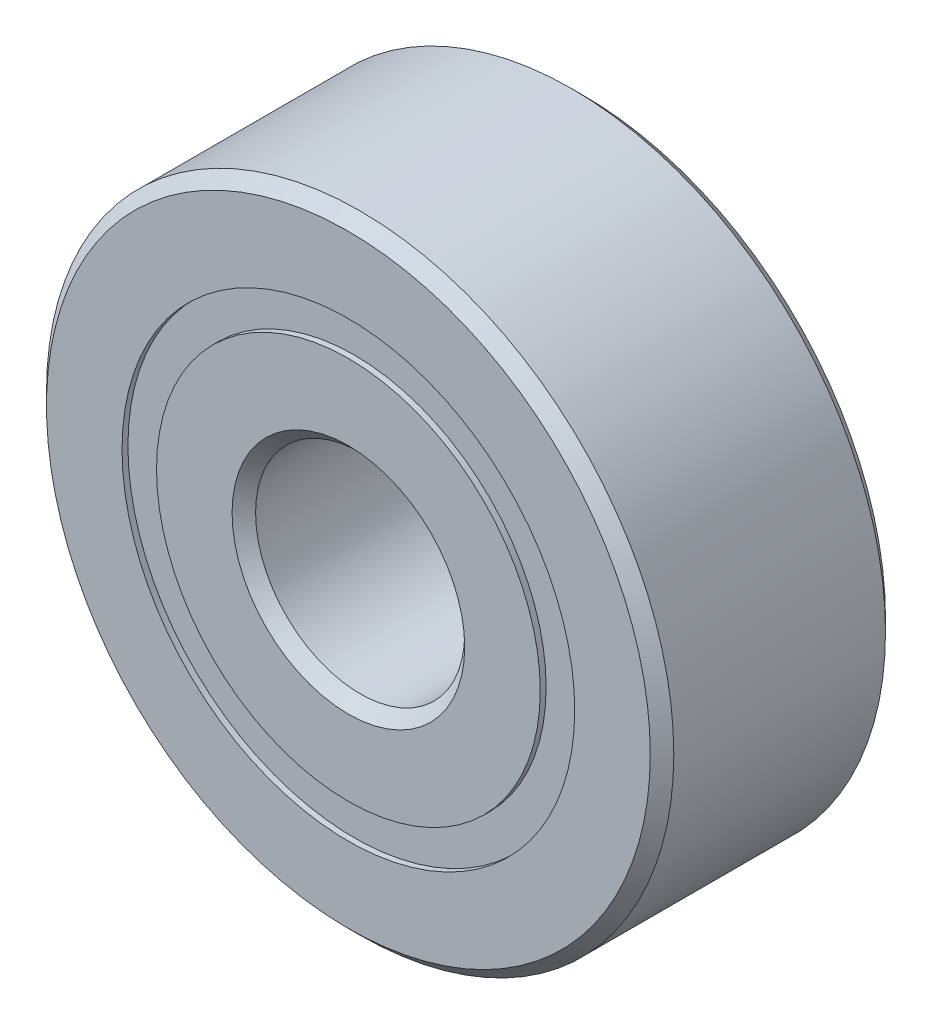
SolidWorks part; units mm, degrees
material "Cast Alloy Steel"
ref_plane "Front Plane" through (0, 0, 0) normal (0, 0, 1) x (1, 0, 0)
ref_plane "Top Plane" through (0, 0, 0) normal (0, 1, 0) x (1, 0, 0)
ref_plane "Right Plane" through (0, 0, 0) normal (1, 0, 0) x (0, 0, -1)
sketch "Sketch1" plane through (0, 0, 0) normal (1, 0, 0) x (0, 0, -1)
  line L0 (-3.5719, 0) -> (3.5719, 0) construction
  line L1 (0, 9.525) -> (0, -9.525) construction
  line L2 (3.2147, 9.525) -> (-3.2147, 9.525)
  line L3 (-3.2147, 9.525) -> (-3.5719, 9.1678)
  line L4 (-3.5719, 9.1678) -> (-3.5719, 6.8734)
  line L5 (-3.5719, 6.8734) -> (-1.5875, 6.8734)
  line L6 (3.5719, 6.8734) -> (1.5875, 6.8734)
  line L7 (3.5719, 9.1678) -> (3.5719, 6.8734)
  line L8 (3.2147, 9.525) -> (3.5719, 9.1678)
  line L9 (0, 9.525) -> (0, 6.35) construction
  line L10 (0, 6.35) -> (0, 3.175) construction
  arc A0 (-1.5875, 6.8734) -> (1.5875, 6.8734) centre (0, 6.35) cw
  point P14 (0, 3.175)
  dimension "D3" = 3.175
  dimension "D1" = 45
  dimension "Width" = 7.1437
  dimension "OD" = 19.05
  dimension "D2" = 0.3572
  dimension "Shaft Dia" = 6.35
  dimension "D4" = 0.5234
revolve "Revolve1" add sketch "Sketch1" angle 360 about L0
sketch "Sketch3" plane through (0, 0, 0) normal (1, 0, 0) x (0, 0, -1)
  line L0 (-3.5719, 5.8266) -> (-1.5875, 5.8266)
  line L1 (0, 9.525) -> (0, -9.525) construction
  line L2 (-3.5719, 9.1678) -> (-3.5719, 6.8734) construction
  line L3 (-3.5719, 5.8266) -> (-3.5719, 3.5322)
  line L4 (-3.2147, 9.525) -> (-3.5719, 9.1678) construction
  line L5 (-3.5719, 3.5322) -> (-3.2147, 3.175)
  line L6 (-3.2147, 3.175) -> (3.2147, 3.175)
  line L7 (3.2147, 9.525) -> (3.2147, -9.525) construction
  line L8 (3.2147, 3.175) -> (3.5719, 3.5322)
  line L9 (3.5719, -9.1678) -> (3.5719, 9.1678) construction
  line L10 (3.5719, 3.5322) -> (3.5719, 5.8266)
  line L11 (3.5719, 5.8266) -> (1.5875, 5.8266)
  line L13 (3.2147, 9.525) -> (3.5719, 9.1678) construction
  arc A0 (1.5875, 6.8734) -> (-1.5875, 6.8734) centre (0, 6.35) ccw construction
  arc A1 (1.5875, 5.8266) -> (-1.5875, 5.8266) centre (0, 6.35) cw
revolve "Revolve3" add sketch "Sketch3" angle 360 about L0
sketch "Sketch4" plane through (0, 0, 0) normal (1, 0, 0) x (0, 0, -1)
  line L0 (-1.6715, 6.35) -> (1.6715, 6.35)
  arc A2 (-1.6715, 6.35) -> (1.6715, 6.35) centre (0, 6.35) cw
  arc A3 (1.5875, 6.8734) -> (-1.5875, 6.8734) centre (0, 6.35) ccw construction
revolve "Revolve4" add sketch "Sketch4" angle 360 about L0
ref_axis "Axis1" through (0, 0, -3.5719) along (0, 0, 1)
pattern_circular "CirPattern1" count 8 every 45 about axis through (0, 0, -3.5719) along (0, 0, 1) of bodies 104
sketch "Sketch5" plane through (0, 0, 0) normal (1, 0, 0) x (0, 0, -1)
  line L0 (-3.5719, 6.8734) -> (-1.5875, 6.8734) construction
  line L1 (-3.3933, 6.8734) -> (-1.6715, 6.8734)
  line L2 (-3.3933, 6.8734) -> (-3.3933, 5.8266)
  line L3 (-3.3933, 5.8266) -> (-1.6715, 5.8266)
  line L4 (-1.6715, 6.8734) -> (-1.6715, 5.8266)
  line L5 (-3.5719, 5.8266) -> (-1.5875, 5.8266) construction
  line L6 (3.5719, 6.8734) -> (1.5875, 6.8734) construction
  line L7 (3.3933, 6.8734) -> (1.6715, 6.8734)
  line L8 (3.3933, 6.8734) -> (3.3933, 5.8266)
  line L9 (3.3933, 5.8266) -> (1.6715, 5.8266)
  line L10 (1.6715, 6.8734) -> (1.6715, 5.8266)
  line L11 (3.5719, 5.8266) -> (1.5875, 5.8266) construction
  line L12 (-3.2147, 9.525) -> (-3.5719, 9.1678) construction
  point P18 (-3.3933, 9.3464)
revolve "Revolve5" add sketch "Sketch5" angle 360 about L0
equation "\"D2@Sketch1\" = \"Width@Sketch1\"*.05"
equation "\"D3@Sketch1\" = \"Width@Sketch1\"/2.25"
equation "\"D4@Sketch1\" = (((\"OD@Sketch1\"-\"Width@Sketch1\")/2)/3.25)/3.5"
equation "\"D2@CirPattern1\" = 360/\"Balls@CirPattern1\""
